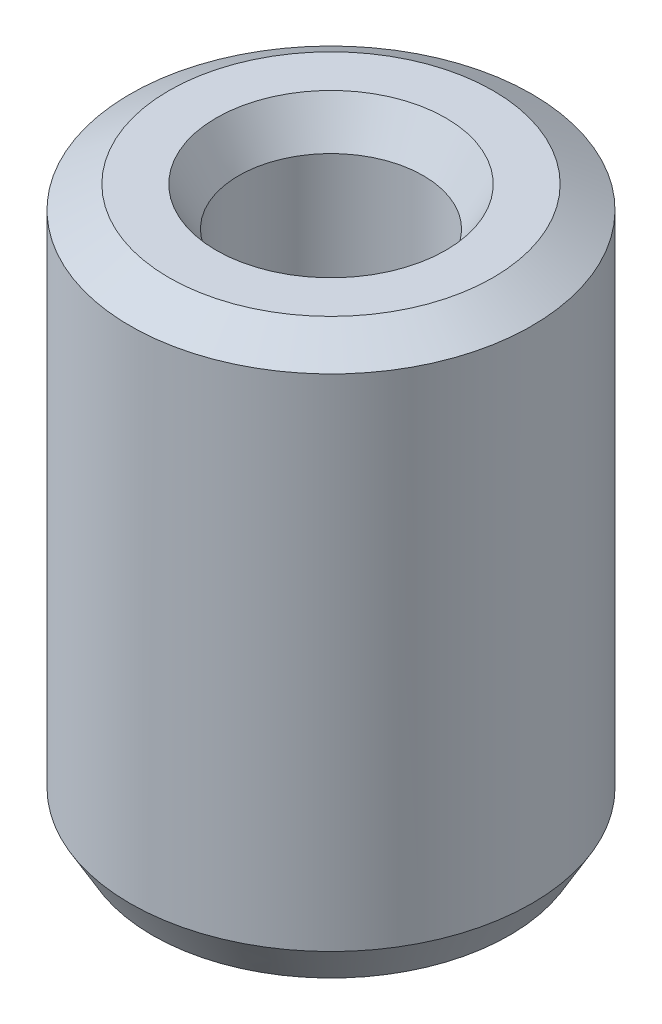
SolidWorks part; units mm, degrees
ref_plane "Front Plane" through (0, 0, 0) normal (0, 0, 1) x (1, 0, 0)
ref_plane "Top Plane" through (0, 0, 0) normal (0, 1, 0) x (1, 0, 0)
ref_plane "Right Plane" through (0, 0, 0) normal (1, 0, 0) x (0, 0, -1)
sketch "Sketch1" plane through (0, 0, 0) normal (0, 1, 0) x (1, 0, 0)
  circle A0 centre (0, 0) radius 20
  dimension "SLEEVE_OD" = 40
extrude "Boss-Extrude1" add sketch "Sketch1" along normal blind 55.9059
sketch "Sketch2" plane through (0, 0, 0) normal (0, 1, 0) x (1, 0, 0)
  circle A0 centre (0, 0) radius 9.1958
  dimension "BORE_D" = 18.3915
extrude "Cut-Extrude1" cut sketch "Sketch2" along normal through all
chamfer "Chamfer1" distance 2.2308 angle 60 4 edges at (0, 55.9059, 9.1958) (0, 0, 9.1958) (0, 0, 20) (0, 55.9059, 20) first distance on face at (0, 55.9059, 9.1958) first distance on face at (0, 0, 9.1958) first distance on face at (0, 55.9059, 20)
